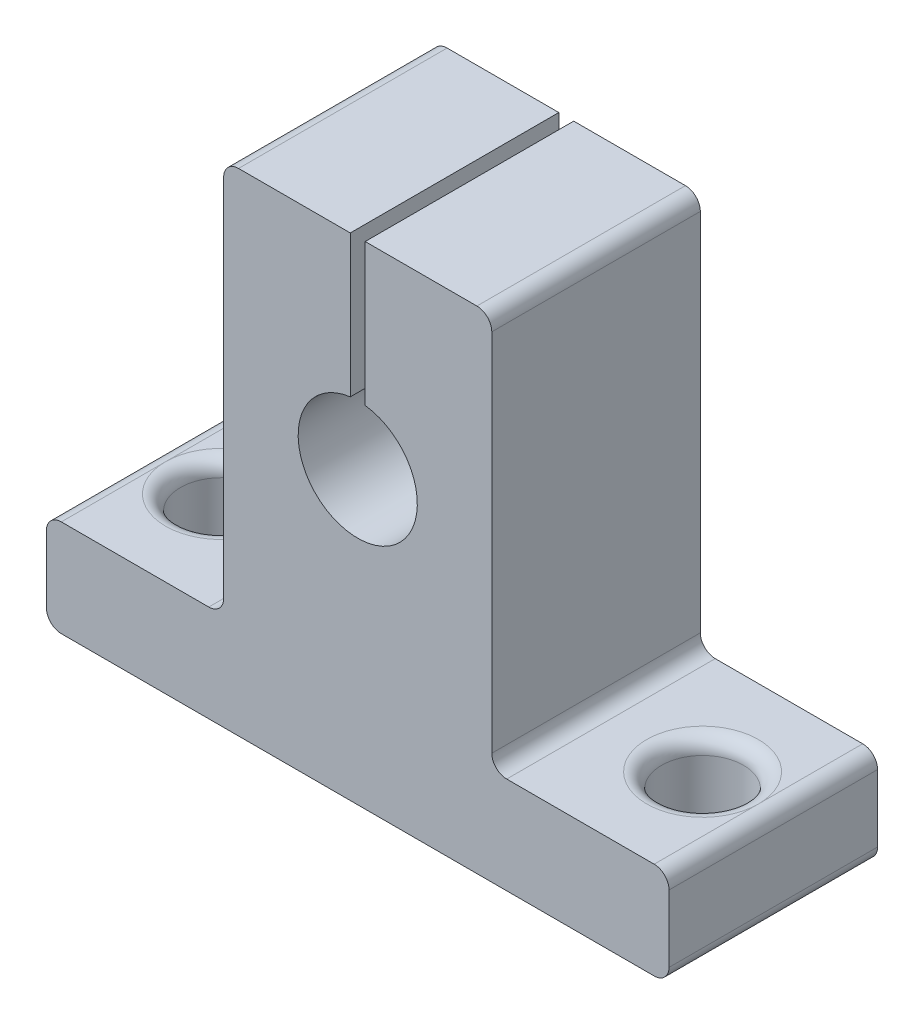
SolidWorks part; units mm, degrees
ref_plane "前视基准面" through (0, 0, 0) normal (0, 0, 1) x (1, 0, 0)
ref_plane "上视基准面" through (0, 0, 0) normal (0, 1, 0) x (1, 0, 0)
ref_plane "右视基准面" through (0, 0, 0) normal (1, 0, 0) x (0, 0, -1)
sketch "草图1" plane through (0, 0, 0) normal (0, 0, 1) x (1, 0, 0)
  line L0 (-0.5, 33) -> (-8, 33)
  line L1 (-9, 32) -> (-9, 7.5)
  line L2 (-10, 6.5) -> (-19.9, 6.5)
  line L3 (-20.9, 5.5) -> (-20.9, 1)
  line L4 (-19.9, 0) -> (19.9, 0)
  line L5 (-0.5, 33) -> (-0.5, 23.4686)
  line L6 (0, -55) -> (0, 55) construction
  line L7 (0.5, 33) -> (0.5, 23.4686)
  line L8 (20.9, 5.5) -> (20.9, 1)
  line L9 (10, 6.5) -> (19.9, 6.5)
  line L10 (9, 32) -> (9, 7.5)
  line L11 (0.5, 33) -> (8, 33)
  arc A0 (-0.5, 23.4686) -> (0.5, 23.4686) centre (0, 19.5) ccw
  arc A1 (-8, 33) -> (-9, 32) centre (-8, 32) ccw
  arc A2 (9, 32) -> (8, 33) centre (8, 32) ccw
  arc A3 (10, 6.5) -> (9, 7.5) centre (10, 7.5) cw
  arc A4 (20.9, 5.5) -> (19.9, 6.5) centre (19.9, 5.5) ccw
  arc A5 (20.9, 1) -> (19.9, 0) centre (19.9, 1) cw
  arc A6 (-20.9, 1) -> (-19.9, 0) centre (-19.9, 1) ccw
  arc A7 (-19.9, 6.5) -> (-20.9, 5.5) centre (-19.9, 5.5) ccw
  arc A8 (-9, 7.5) -> (-10, 6.5) centre (-10, 7.5) cw
  point P15 (0, 0)
  point P19 (-9, 33)
  point P22 (9, 33)
  point P25 (9, 6.5)
  point P28 (20.9, 6.5)
  point P31 (20.9, 0)
  point P34 (-20.9, 0)
  point P37 (-20.9, 6.5)
  point P40 (-9, 6.5)
  dimension "D6" = 8
  dimension "D8" = 1
  dimension "D1" = 8.5
  dimension "D2" = 0.5
  dimension "D3" = 26.5
  dimension "D4" = 6.5
  dimension "D5" = 20.9
  dimension "D7" = 13.5
extrude "凸台-拉伸1" add sketch "草图1" along normal blind 14
sketch "草图2" plane through (0, 0, 0) normal (0, 1, 0) x (1, 0, 0)
  line L0 (20.9, -14) -> (20.9, 0) construction
  line L1 (0, -7.7) -> (0, 7.7) construction
  circle A0 centre (16.15, -7) radius 2.75
  circle A1 centre (-16.15, -7) radius 2.75
  dimension "D1" = 5.5
  dimension "D2" = 7
  dimension "D3" = 4.75
extrude "切除-拉伸1" cut sketch "草图2" along normal blind 14
fillet "圆角1" radius 1 4 edges at (18.9, 6.5, 7) (16.15, 0, 9.75) (-13.4, 6.5, 7) (-16.15, 0, 4.25)
